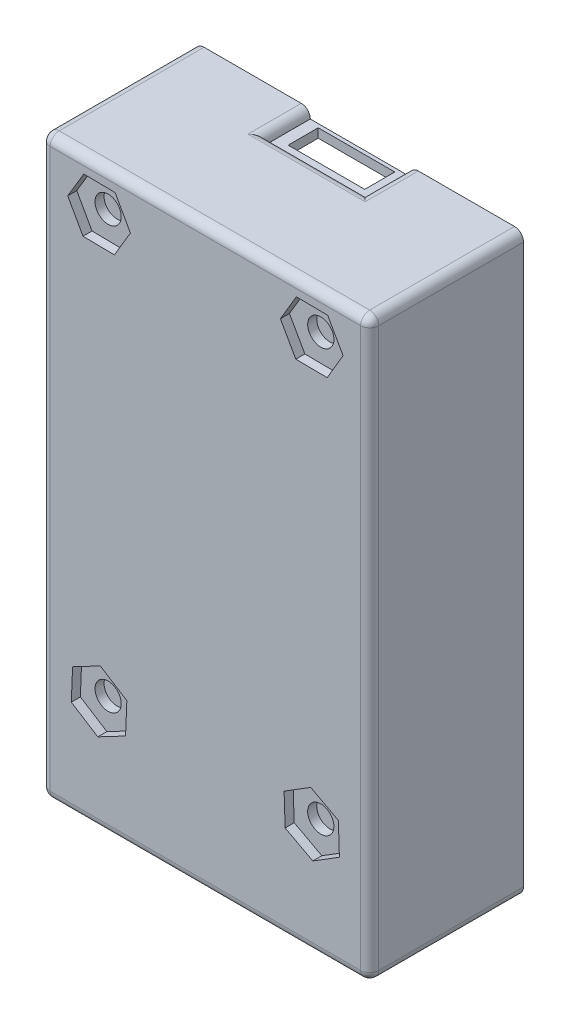
SolidWorks part; units mm, degrees
ref_plane "Alzado" through (0, 0, 0) normal (0, 0, 1) x (1, 0, 0)
ref_plane "Planta" through (0, 0, 0) normal (0, 1, 0) x (1, 0, 0)
ref_plane "Vista lateral" through (0, 0, 0) normal (1, 0, 0) x (0, 0, -1)
sketch "Croquis1" plane through (0, 0, 0) normal (0, 0, 1) x (1, 0, 0)
  line L0 (-9.715, 23.9209) -> (-9.715, -24.2791) construction
  line L1 (-13.715, 27.9209) -> (22.585, 27.9209)
  line L2 (-13.715, 27.9209) -> (-13.715, -35.7791)
  line L3 (-13.715, -35.7791) -> (22.585, -35.7791)
  line L4 (22.585, 27.9209) -> (22.585, -35.7791)
  line L5 (18.585, -24.2791) -> (18.585, 23.9209) construction
  line L6 (-8.215, -25.7791) -> (17.085, -25.7791) construction
  line L7 (17.085, 25.4209) -> (-8.215, 25.4209) construction
  dimension "D1" = 4
  dimension "D2" = 4
  dimension "D3" = 10
  dimension "D4" = 2.5
extrude "Saliente-Extruir1" add sketch "Croquis1" along normal blind 2
sketch "Croquis2" plane through (0, 0, 0) normal (0, 0, -1) x (-1, 0, 0)
  circle A0 centre (-16.185, 23.1209) radius 1.45
  circle A1 centre (7.315, 23.1209) radius 1.45
  circle A2 centre (7.315, -23.4791) radius 1.45
  circle A3 centre (-16.185, -23.4791) radius 1.45
extrude "Cortar-Extruir1" cut sketch "Croquis2" against normal through all
sketch "Croquis3" plane through (0, 0, 0) normal (0, 0, -1) x (-1, 0, 0)
  line L1 (-22.585, 27.9209) -> (13.715, 27.9209)
  line L2 (-22.585, 27.9209) -> (-22.585, -35.7791)
  line L3 (-22.585, -35.7791) -> (13.715, -35.7791)
  line L4 (13.715, 27.9209) -> (13.715, -35.7791)
  line L5 (-20.585, 25.9209) -> (11.715, 25.9209)
  line L6 (-20.585, 25.9209) -> (-20.585, -33.7791)
  line L7 (-20.585, -33.7791) -> (11.715, -33.7791)
  line L8 (11.715, 25.9209) -> (11.715, -33.7791)
  dimension "D1" = 2
  dimension "D2" = 2
  dimension "D3" = 2
  dimension "D4" = 2
extrude "Saliente-Extruir2" add sketch "Croquis3" along normal blind 15
sketch "Croquis4" plane through (0, 27.9209, 0) normal (0, 1, 0) x (1, 0, 0)
  line L0 (-3.115, 14.6) -> (12.285, 14.6) construction
  line L1 (8.76, 11.2777) -> (0.3018, 11.2777)
  line L2 (8.76, 11.2777) -> (8.76, 14.6)
  line L3 (8.76, 14.6) -> (0.3018, 14.6)
  line L4 (0.3018, 11.2777) -> (0.3018, 14.6)
extrude "Cortar-Extruir2" cut sketch "Croquis4" against normal blind 15
sketch "Croquis5" plane through (0, 27.9209, 0) normal (0, 1, 0) x (1, 0, 0)
  line L0 (-13.715, 15) -> (22.585, 15) construction
  line L1 (-0.9754, 15) -> (9.9722, 15)
  line L2 (-0.9754, 15) -> (-0.9754, 10.1104)
  line L3 (-0.9754, 10.1104) -> (9.9722, 10.1104)
  line L4 (9.9722, 15) -> (9.9722, 10.1104)
extrude "Cortar-Extruir3" cut sketch "Croquis5" against normal blind 1
sketch "Croquis6" plane through (0, 0, 0) normal (0, 0, -1) x (-1, 0, 0)
  circle A0 centre (-16.185, 23.1209) radius 2.4
  circle A1 centre (7.315, 23.1209) radius 2.4
  circle A2 centre (7.315, -23.4791) radius 2.4
  circle A3 centre (-16.185, -23.4791) radius 2.4
extrude "Saliente-Extruir3" add sketch "Croquis6" along normal blind 10
fillet "Redondeo1" radius 1 11 edges at (-0.9754, 27.9209, -12.5552) (4.4984, 27.9209, -10.1104) (9.9722, 27.9209, -12.5552) (22.585, -3.9291, 2) (22.585, -35.7791, -6.5) (4.435, -35.7791, 2) (-13.715, -35.7791, -6.5) (-13.715, -3.9291, 2) (4.435, 27.9209, 2) (-13.715, 27.9209, -6.5) (22.585, 27.9209, -6.5)
sketch "Croquis7" plane through (0, 0, 2) normal (0, 0, 1) x (1, 0, 0)
  line L1 (-5.6269, 20.0959) -> (-3.8512, 23.0704)
  line L2 (-3.8512, 23.0704) -> (-5.5394, 26.0953)
  line L3 (-5.5394, 26.0953) -> (-9.0031, 26.1458)
  line L4 (-9.0031, 26.1458) -> (-10.7787, 23.1714)
  line L5 (-10.7787, 23.1714) -> (-9.0906, 20.1465)
  line L6 (-9.0906, 20.1465) -> (-5.6269, 20.0959)
  line L7 (17.8872, 20.1038) -> (19.649, 23.0865)
  line L8 (19.649, 23.0865) -> (17.9468, 26.1035)
  line L9 (17.9468, 26.1035) -> (14.4828, 26.1379)
  line L10 (14.4828, 26.1379) -> (12.7211, 23.1553)
  line L11 (12.7211, 23.1553) -> (14.4233, 20.1382)
  line L12 (14.4233, 20.1382) -> (17.8872, 20.1038)
  line L13 (-4.3866, -25.3297) -> (-4.2482, -21.8683)
  line L14 (-4.2482, -21.8683) -> (-7.1766, -20.0178)
  line L15 (-7.1766, -20.0178) -> (-10.2434, -21.6286)
  line L16 (-10.2434, -21.6286) -> (-10.3818, -25.0899)
  line L17 (-10.3818, -25.0899) -> (-7.4534, -26.9405)
  line L18 (-7.4534, -26.9405) -> (-4.3866, -25.3297)
  line L19 (19.2404, -25.1114) -> (19.1263, -21.6492)
  line L20 (19.1263, -21.6492) -> (16.0709, -20.0169)
  line L21 (16.0709, -20.0169) -> (13.1296, -21.8468)
  line L22 (13.1296, -21.8468) -> (13.2437, -25.309)
  line L23 (13.2437, -25.309) -> (16.2991, -26.9413)
  line L24 (16.2991, -26.9413) -> (19.2404, -25.1114)
  circle A0 centre (-7.315, 23.1209) radius 3 construction
  circle A1 centre (16.185, 23.1209) radius 3 construction
  circle A2 centre (-7.315, -23.4791) radius 3 construction
  circle A3 centre (16.185, -23.4791) radius 3 construction
  point P1 (-7.2712, 26.1206)
  dimension "D1" = 6
  dimension "D2" = 6
  dimension "D3" = 6
  dimension "D4" = 6
extrude "Cortar-Extruir4" cut sketch "Croquis7" against normal blind 1
